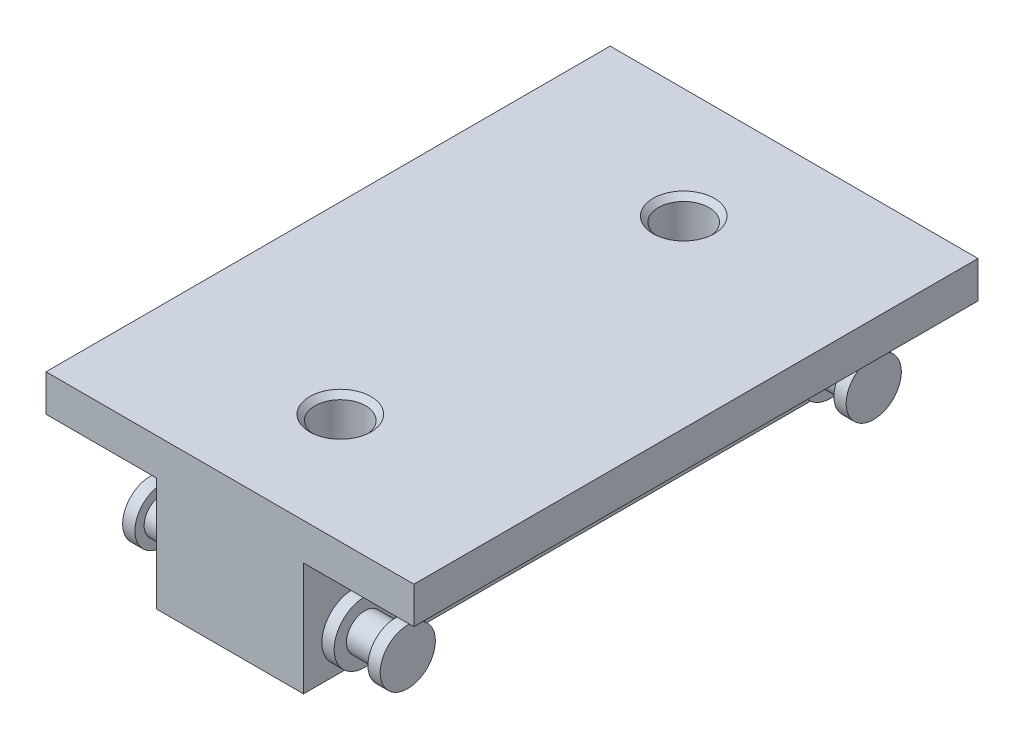
SolidWorks part; units mm, degrees
ref_plane "Front Plane" through (0, 0, 0) normal (0, 0, 1) x (1, 0, 0)
ref_plane "Top Plane" through (0, 0, 0) normal (0, 1, 0) x (1, 0, 0)
ref_plane "Right Plane" through (0, 0, 0) normal (1, 0, 0) x (0, 0, -1)
ref_plane "Plane1" through (0, 0, 0) normal (0, 0, 1) x (1, 0, 0)
sketch "Sketch1" plane through (0, 0, 0) normal (0, 0, 1) x (1, 0, 0)
  line L0 (-15, 6.25) -> (-15, 3.25)
  line L1 (-15, 3.25) -> (-6, 3.25)
  line L2 (-6, 3.25) -> (-6, -6)
  line L3 (-6, -6) -> (6, -6)
  line L4 (6, -6) -> (6, 3.25)
  line L5 (6, 3.25) -> (15, 3.25)
  line L6 (15, 3.25) -> (15, 6.25)
  line L7 (15, 6.25) -> (-15, 6.25)
extrude "Boss-Extrude1" add sketch "Sketch1" against normal blind 23 and the other way blind 23
ref_plane "Plane2" through (0, 0, 19) normal (0, 0, 1) x (1, 0, 0)
sketch "Sketch2" plane through (0, 0, 19) normal (0, 0, 1) x (1, 0, 0)
  line L0 (10.5, -3.125) -> (10.5, -5.375)
  line L1 (10.5, -5.375) -> (9.5, -5.375)
  line L2 (9.5, -5.375) -> (9.5, -4.625)
  line L3 (9.5, -4.625) -> (7, -4.625)
  line L4 (7, -4.625) -> (7, -5.625)
  line L5 (7, -5.625) -> (6, -5.625)
  line L6 (6, -5.625) -> (6, -4.625)
  line L7 (6, -4.625) -> (-6, -4.625)
  line L8 (-6, -4.625) -> (-6, -5.625)
  line L9 (-6, -5.625) -> (-7, -5.625)
  line L10 (-7, -5.625) -> (-7, -4.625)
  line L11 (-7, -4.625) -> (-9.5, -4.625)
  line L12 (-9.5, -4.625) -> (-9.5, -5.375)
  line L13 (-9.5, -5.375) -> (-10.5, -5.375)
  line L14 (-10.5, -5.375) -> (-10.5, -3.125)
  line L15 (-10.5, -3.125) -> (10.5, -3.125)
  line L16 (-10.5, -3.125) -> (10.5, -3.125) construction
revolve "Revolve1" add sketch "Sketch2" angle 360 about L16 reverse direction yes
ref_plane "Plane3" through (0, 0, -19) normal (0, 0, 1) x (1, 0, 0)
sketch "Sketch3" plane through (0, 0, -19) normal (0, 0, 1) x (1, 0, 0)
  line L0 (10.5, -3.125) -> (10.5, -5.375)
  line L1 (10.5, -5.375) -> (9.5, -5.375)
  line L2 (9.5, -5.375) -> (9.5, -4.625)
  line L3 (9.5, -4.625) -> (7, -4.625)
  line L4 (7, -4.625) -> (7, -5.625)
  line L5 (7, -5.625) -> (6, -5.625)
  line L6 (6, -5.625) -> (6, -4.625)
  line L7 (6, -4.625) -> (-6, -4.625)
  line L8 (-6, -4.625) -> (-6, -5.625)
  line L9 (-6, -5.625) -> (-7, -5.625)
  line L10 (-7, -5.625) -> (-7, -4.625)
  line L11 (-7, -4.625) -> (-9.5, -4.625)
  line L12 (-9.5, -4.625) -> (-9.5, -5.375)
  line L13 (-9.5, -5.375) -> (-10.5, -5.375)
  line L14 (-10.5, -5.375) -> (-10.5, -3.125)
  line L15 (-10.5, -3.125) -> (10.5, -3.125)
  line L16 (-10.5, -3.125) -> (10.5, -3.125) construction
revolve "Revolve2" add sketch "Sketch3" angle 360 about L16 reverse direction yes
ref_plane "Plane4" through (0, 0, 0) normal (1, 0, 0) x (0, 0, -1)
sketch "Sketch4" plane through (0, 0, 0) normal (1, 0, 0) x (0, 0, -1)
  line L0 (-14, 6.25) -> (-11.5, 6.25)
  line L1 (-11.5, 6.25) -> (-11.933, 5.817)
  line L2 (-11.933, 5.817) -> (-11.933, -5.567)
  line L3 (-11.933, -5.567) -> (-11.5, -6)
  line L4 (-11.5, -6) -> (-14, -6)
  line L5 (-14, -6) -> (-14, 6.25)
  line L6 (-14, -6) -> (-14, 6.25) construction
revolve "Cut-Revolve1" cut sketch "Sketch4" angle 360 about L6 reverse direction yes
ref_plane "Plane5" through (0, 0, 0) normal (1, 0, 0) x (0, 0, -1)
sketch "Sketch5" plane through (0, 0, 0) normal (1, 0, 0) x (0, 0, -1)
  line L0 (14, 6.25) -> (16.5, 6.25)
  line L1 (16.5, 6.25) -> (16.067, 5.817)
  line L2 (16.067, 5.817) -> (16.067, -5.567)
  line L3 (16.067, -5.567) -> (16.5, -6)
  line L4 (16.5, -6) -> (14, -6)
  line L5 (14, -6) -> (14, 6.25)
  line L6 (14, -6) -> (14, 6.25) construction
revolve "Cut-Revolve2" cut sketch "Sketch5" angle 360 about L6 reverse direction yes
